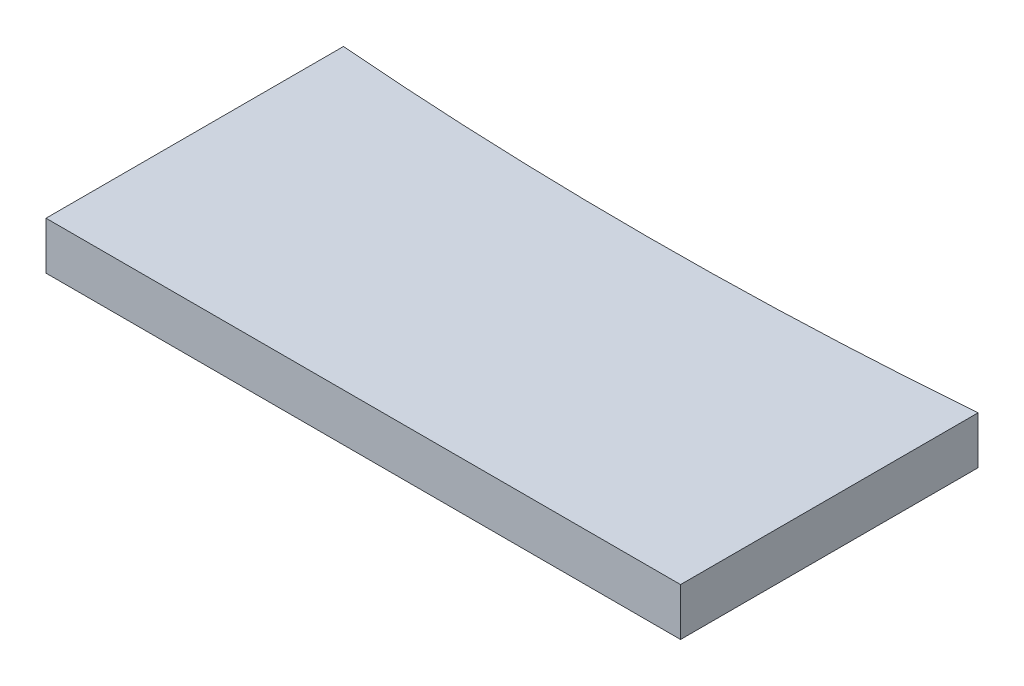
SolidWorks part; units mm, degrees
material "6061 Alloy"
ref_plane "Front Plane" through (0, 0, 0) normal (0, 0, 1) x (1, 0, 0)
ref_plane "Top Plane" through (0, 0, 0) normal (0, 1, 0) x (1, 0, 0)
ref_plane "Right Plane" through (0, 0, 0) normal (1, 0, 0) x (0, 0, -1)
sketch "Sketch1" plane through (0, 0, 0) normal (0, 1, 0) x (1, 0, 0)
  line L0 (-5.08, -63.2965) -> (-5.08, -66.4812)
  line L1 (5.08, -63.2965) -> (5.08, -66.4812)
  line L2 (-5.08, -68.059) -> (5.08, -68.059)
  line L3 (-5.08, -66.4812) -> (-5.08, -68.059)
  line L4 (5.08, -66.4812) -> (5.08, -68.059)
  circle A0 centre (0, 0) radius 63.5
  circle A1 centre (0, 0) radius 66.675
  dimension "D1" = 127
  dimension "D3" = 5.08
  dimension "D4" = 5.08
  dimension "D5" = 4.7625
  dimension "D2" = 3.175
extrude "Boss-Extrude1" add sketch "Sketch1" along normal blind 0.762 contours L0 A1 L1 A0 | A1 L3 L2 | A1 L2 L4 region at (0, 0, 65.0213) region at (0, 0, 67.3336)
sketch "Sketch2" plane through (0, 0, 0) normal (0, 0, 1) x (1, 0, 0)
  line L0 (0, 12.7) -> (0, 0) construction
  line L5 (-5.08, 0) -> (5.08, 0)
  line L6 (5.08, 0) -> (5.08, 0.762)
  line L7 (5.08, 0.762) -> (-5.08, 0.762)
  line L12 (-5.08, 0.762) -> (-5.08, 0)
  line L13 (-5.08, 0) -> (5.08, 0)
  line L14 (5.08, 0) -> (5.08, 0.762)
  line L15 (5.08, 0.762) -> (-5.08, 0.762)
  line L16 (-5.08, 0.762) -> (-5.08, 0)
  dimension "D1" = 0
equation "\"Middle Coupler Inner Daimeter\"= 4.5in"
equation "\"Middle Coupler  Wall Thickness\" = 0.25in"
equation "\"Middle Coupler Bottom Thickness\"= 0.2in"
equation "\"Bearing Rail Offset\"= 0.45in"
equation "\"3-56 UNF Tap\"= 0.089in"
equation "\"3-56 UNF Clearance\"= 0.104in"
equation "\"Ball Bearing Distance\"= 0.03in"
equation "\"TCA Outer Diameter\" = 6.625in"
equation "\"D1@Sketch1\"=\"Middle Coupler Inner Daimeter\"+0.5"
equation "\"D2@Sketch1\"=1/8"
equation "\"Interstage Aeroframe Wall Thickness\" = 0.072in"
equation "\"Compression Spring OD\"= 0.42in"
equation "\"10-24 Tap\"= 0.157in"
equation "\"10-24 Clearance\"= 0.196in"
equation "\"Lower Stage Fuselage Wall Thickness\" = 0.25in"
equation "\"6-32 Tap\" = 0.107in"
equation "\"1/4-20 Tap\" = 0.201in"
equation "\"3-48 Tap\"= 0.079in"
equation "\"3-48 Clearance\" = 0.104in"
equation "\"6-32 Clearance\" = 0.144"
equation "\"12-24 Tap\" = 0.177in"
equation "\"D5@Sketch1\"=3/16"
